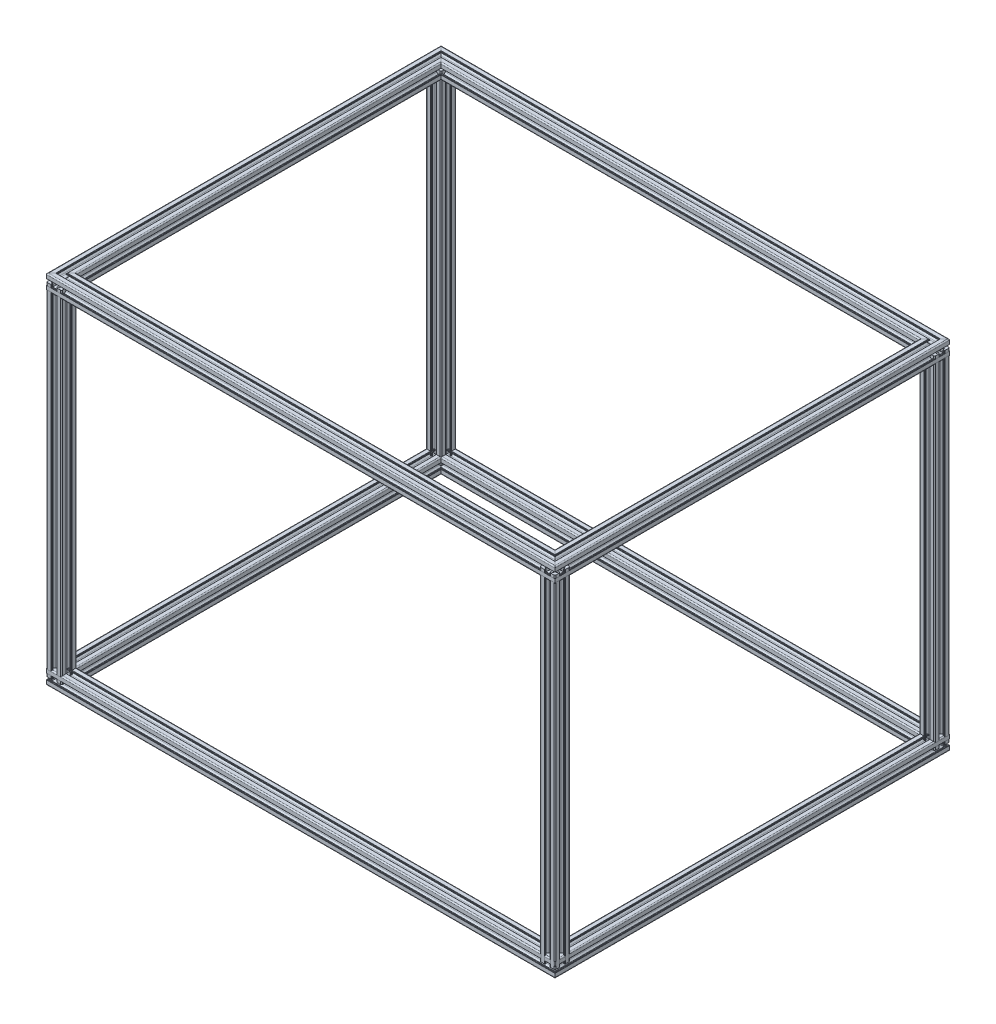
SolidWorks part; units mm, degrees
ref_plane "前视基准面" through (0, 0, 0) normal (0, 0, 1) x (1, 0, 0)
ref_plane "上视基准面" through (0, 0, 0) normal (0, 1, 0) x (1, 0, 0)
ref_plane "右视基准面" through (0, 0, 0) normal (1, 0, 0) x (0, 0, -1)
sketch3d "3D草图1"
  line L0 (0, 0, 0) -> (0, 0, 500)
  line L1 (0, 0, 500) -> (650, 0, 500)
  line L2 (0, 0, 0) -> (650, 0, 0)
  line L3 (650, 0, 0) -> (650, 0, 500)
  line L4 (0, 0, 0) -> (0, -450, 0)
  line L5 (0, -450, 0) -> (0, -450, 500)
  line L6 (0, -450, 500) -> (650, -450, 500)
  line L7 (650, -450, 500) -> (650, -450, 0)
  line L8 (0, -450, 0) -> (650, -450, 0)
  line L9 (0, 0, 500) -> (0, -450, 500)
  line L10 (650, 0, 500) -> (650, -450, 500)
  line L11 (650, 0, 0) -> (650, -450, 0)
  dimension "D1" = 650
  dimension "D2" = 650
  dimension "D3" = 500
  dimension "D4" = 650
  dimension "D5" = 650
  dimension "D6" = 500
  dimension "D7" = 450
other "铝型材库 2020(1)" corner treatment miter
ref_plane "基准面5" through (0, 0, 500) normal (1, 0, 0) x (0, 0, -1)
sketch "草图1" plane through (0, 0, 500) normal (1, 0, 0) x (0, 0, -1)
  line L0 (3.9, 0) -> (3.9, -2.0109)
  line L1 (4.4858, -3.4251) -> (6.5607, -5.5)
  line L2 (6.5607, -5.5) -> (7.9, -5.5)
  line L3 (8.2, -5.2) -> (8.2, -3.4)
  line L4 (8.5, -3.1) -> (9.2, -3.1)
  line L5 (9.5, -3.4) -> (9.5, -3.6)
  line L6 (9.5, -3.6) -> (9.7, -3.6)
  line L7 (10, -3.9) -> (10, -8.5)
  line L8 (8.5, -10) -> (3.9, -10)
  line L9 (3.1, -9.2) -> (3.1, -8.5)
  line L10 (3.4, -8.2) -> (5.2, -8.2)
  line L11 (5.5, -7.9) -> (5.5, -6.6849)
  line L12 (5.4121, -6.4728) -> (3.4251, -4.4858)
  line L13 (2.0109, -3.9) -> (0, -3.9)
  line L14 (0, -3.9) -> (-2.0109, -3.9)
  line L15 (-3.4251, -4.4858) -> (-5.4121, -6.4728)
  line L16 (-5.5, -6.6849) -> (-5.5, -7.9)
  line L17 (-5.2, -8.2) -> (-3.4, -8.2)
  line L18 (-3.1, -8.5) -> (-3.1, -9.2)
  line L19 (-3.9, -10) -> (-8.5, -10)
  line L20 (-10, -8.5) -> (-10, -3.9)
  line L21 (-9.7, -3.6) -> (-9.5, -3.6)
  line L22 (-9.5, -3.6) -> (-9.5, -3.4)
  line L23 (-9.2, -3.1) -> (-8.5, -3.1)
  line L24 (-8.2, -3.4) -> (-8.2, -5.2)
  line L25 (-7.9, -5.5) -> (-6.6849, -5.5)
  line L26 (-6.4728, -5.4121) -> (-4.4858, -3.4251)
  line L27 (-3.9, -2.0109) -> (-3.9, 0)
  line L28 (-3.9, 0) -> (-3.9, 2.0109)
  line L29 (-4.4858, 3.4251) -> (-6.4728, 5.4121)
  line L30 (-6.6849, 5.5) -> (-7.9, 5.5)
  line L31 (-8.2, 5.2) -> (-8.2, 3.4)
  line L32 (-8.5, 3.1) -> (-9.2, 3.1)
  line L33 (-9.5, 3.4) -> (-9.5, 3.6)
  line L34 (-9.5, 3.6) -> (-9.7, 3.6)
  line L35 (-10, 3.9) -> (-10, 8.5)
  line L36 (-8.5, 10) -> (-3.9, 10)
  line L37 (-3.6, 9.7) -> (-3.6, 9.5)
  line L38 (-3.6, 9.5) -> (-3.4, 9.5)
  line L39 (-3.1, 9.2) -> (-3.1, 8.5)
  line L40 (-3.4, 8.2) -> (-5.2, 8.2)
  line L41 (-5.5, 7.9) -> (-5.5, 6.6849)
  line L42 (-5.4121, 6.4728) -> (-3.4251, 4.4858)
  line L43 (-2.0109, 3.9) -> (0, 3.9)
  line L44 (0, 3.9) -> (2.0109, 3.9)
  line L45 (3.4251, 4.4858) -> (5.4121, 6.4728)
  line L46 (5.5, 6.6849) -> (5.5, 7.9)
  line L47 (5.2, 8.2) -> (3.4, 8.2)
  line L48 (3.1, 8.5) -> (3.1, 9.2)
  line L49 (3.4, 9.5) -> (3.6, 9.5)
  line L50 (3.6, 9.5) -> (3.6, 9.7)
  line L51 (3.9, 10) -> (8.5, 10)
  line L52 (10, 8.5) -> (10, 3.9)
  line L53 (9.7, 3.6) -> (9.5, 3.6)
  line L54 (9.5, 3.6) -> (9.5, 3.4)
  line L55 (9.2, 3.1) -> (8.5, 3.1)
  line L56 (8.2, 3.4) -> (8.2, 5.2)
  line L57 (7.9, 5.5) -> (6.6849, 5.5)
  line L58 (6.4728, 5.4121) -> (4.4858, 3.4251)
  line L59 (3.9, 2.0109) -> (3.9, 0)
  circle A0 centre (0, 0) radius 2.5
  arc A1 (3.9, -2.0109) -> (4.4858, -3.4251) centre (5.9, -2.0109) ccw
  arc A2 (7.9, -5.5) -> (8.2, -5.2) centre (7.9, -5.2) ccw
  arc A3 (8.5, -3.1) -> (8.2, -3.4) centre (8.5, -3.4) ccw
  arc A4 (9.5, -3.4) -> (9.2, -3.1) centre (9.2, -3.4) ccw
  arc A5 (10, -3.9) -> (9.7, -3.6) centre (9.7, -3.9) ccw
  arc A6 (8.5, -10) -> (10, -8.5) centre (8.5, -8.5) ccw
  arc A7 (3.6, -9.7) -> (3.9, -10) centre (3.9, -9.7) ccw
  arc A8 (3.6, -9.7) -> (3.4, -9.5) centre (3.4, -9.7) ccw
  arc A9 (3.1, -9.2) -> (3.4, -9.5) centre (3.4, -9.2) ccw
  arc A10 (3.4, -8.2) -> (3.1, -8.5) centre (3.4, -8.5) ccw
  arc A11 (5.2, -8.2) -> (5.5, -7.9) centre (5.2, -7.9) ccw
  arc A12 (5.5, -6.6849) -> (5.4121, -6.4728) centre (5.2, -6.6849) ccw
  arc A13 (3.4251, -4.4858) -> (2.0109, -3.9) centre (2.0109, -5.9) ccw
  arc A14 (-2.0109, -3.9) -> (-3.4251, -4.4858) centre (-2.0109, -5.9) ccw
  arc A15 (-5.4121, -6.4728) -> (-5.5, -6.6849) centre (-5.2, -6.6849) ccw
  arc A16 (-5.5, -7.9) -> (-5.2, -8.2) centre (-5.2, -7.9) ccw
  arc A17 (-3.1, -8.5) -> (-3.4, -8.2) centre (-3.4, -8.5) ccw
  arc A18 (-3.4, -9.5) -> (-3.1, -9.2) centre (-3.4, -9.2) ccw
  arc A19 (-3.4, -9.5) -> (-3.6, -9.7) centre (-3.4, -9.7) ccw
  arc A20 (-3.9, -10) -> (-3.6, -9.7) centre (-3.9, -9.7) ccw
  arc A21 (-10, -8.5) -> (-8.5, -10) centre (-8.5, -8.5) ccw
  arc A22 (-9.7, -3.6) -> (-10, -3.9) centre (-9.7, -3.9) ccw
  arc A23 (-9.2, -3.1) -> (-9.5, -3.4) centre (-9.2, -3.4) ccw
  arc A24 (-8.2, -3.4) -> (-8.5, -3.1) centre (-8.5, -3.4) ccw
  arc A25 (-8.2, -5.2) -> (-7.9, -5.5) centre (-7.9, -5.2) ccw
  arc A26 (-6.6849, -5.5) -> (-6.4728, -5.4121) centre (-6.6849, -5.2) ccw
  arc A27 (-4.4858, -3.4251) -> (-3.9, -2.0109) centre (-5.9, -2.0109) ccw
  arc A28 (-3.9, 2.0109) -> (-4.4858, 3.4251) centre (-5.9, 2.0109) ccw
  arc A29 (-6.4728, 5.4121) -> (-6.6849, 5.5) centre (-6.6849, 5.2) ccw
  arc A30 (-7.9, 5.5) -> (-8.2, 5.2) centre (-7.9, 5.2) ccw
  arc A31 (-8.5, 3.1) -> (-8.2, 3.4) centre (-8.5, 3.4) ccw
  arc A32 (-9.5, 3.4) -> (-9.2, 3.1) centre (-9.2, 3.4) ccw
  arc A33 (-10, 3.9) -> (-9.7, 3.6) centre (-9.7, 3.9) ccw
  arc A34 (-8.5, 10) -> (-10, 8.5) centre (-8.5, 8.5) ccw
  arc A35 (-3.6, 9.7) -> (-3.9, 10) centre (-3.9, 9.7) ccw
  arc A36 (-3.1, 9.2) -> (-3.4, 9.5) centre (-3.4, 9.2) ccw
  arc A37 (-3.4, 8.2) -> (-3.1, 8.5) centre (-3.4, 8.5) ccw
  arc A38 (-5.2, 8.2) -> (-5.5, 7.9) centre (-5.2, 7.9) ccw
  arc A39 (-5.5, 6.6849) -> (-5.4121, 6.4728) centre (-5.2, 6.6849) ccw
  arc A40 (-3.4251, 4.4858) -> (-2.0109, 3.9) centre (-2.0109, 5.9) ccw
  arc A41 (2.0109, 3.9) -> (3.4251, 4.4858) centre (2.0109, 5.9) ccw
  arc A42 (5.4121, 6.4728) -> (5.5, 6.6849) centre (5.2, 6.6849) ccw
  arc A43 (5.5, 7.9) -> (5.2, 8.2) centre (5.2, 7.9) ccw
  arc A44 (3.1, 8.5) -> (3.4, 8.2) centre (3.4, 8.5) ccw
  arc A45 (3.4, 9.5) -> (3.1, 9.2) centre (3.4, 9.2) ccw
  arc A46 (3.9, 10) -> (3.6, 9.7) centre (3.9, 9.7) ccw
  arc A47 (10, 8.5) -> (8.5, 10) centre (8.5, 8.5) ccw
  arc A48 (9.7, 3.6) -> (10, 3.9) centre (9.7, 3.9) ccw
  arc A49 (9.2, 3.1) -> (9.5, 3.4) centre (9.2, 3.4) ccw
  arc A50 (8.2, 3.4) -> (8.5, 3.1) centre (8.5, 3.4) ccw
  arc A51 (8.2, 5.2) -> (7.9, 5.5) centre (7.9, 5.2) ccw
  arc A52 (6.6849, 5.5) -> (6.4728, 5.4121) centre (6.6849, 5.2) ccw
  arc A53 (4.4858, 3.4251) -> (3.9, 2.0109) centre (5.9, 2.0109) ccw
  point P0 (0, 0)
other "铝型材库 2020(2)" corner treatment miter
ref_plane "基准面6" through (650, -450, 500) normal (0, 0, -1) x (1, 0, 0)
sketch "草图113" plane through (650, -450, 500) normal (0, 0, -1) x (1, 0, 0)
  line L0 (3.9, 0) -> (3.9, -2.0109)
  line L1 (4.4858, -3.4251) -> (6.5607, -5.5)
  line L2 (6.5607, -5.5) -> (7.9, -5.5)
  line L3 (8.2, -5.2) -> (8.2, -3.4)
  line L4 (8.5, -3.1) -> (9.2, -3.1)
  line L5 (9.5, -3.4) -> (9.5, -3.6)
  line L6 (9.5, -3.6) -> (9.7, -3.6)
  line L7 (10, -3.9) -> (10, -8.5)
  line L8 (8.5, -10) -> (3.9, -10)
  line L9 (3.1, -9.2) -> (3.1, -8.5)
  line L10 (3.4, -8.2) -> (5.2, -8.2)
  line L11 (5.5, -7.9) -> (5.5, -6.6849)
  line L12 (5.4121, -6.4728) -> (3.4251, -4.4858)
  line L13 (2.0109, -3.9) -> (0, -3.9)
  line L14 (0, -3.9) -> (-2.0109, -3.9)
  line L15 (-3.4251, -4.4858) -> (-5.4121, -6.4728)
  line L16 (-5.5, -6.6849) -> (-5.5, -7.9)
  line L17 (-5.2, -8.2) -> (-3.4, -8.2)
  line L18 (-3.1, -8.5) -> (-3.1, -9.2)
  line L19 (-3.9, -10) -> (-8.5, -10)
  line L20 (-10, -8.5) -> (-10, -3.9)
  line L21 (-9.7, -3.6) -> (-9.5, -3.6)
  line L22 (-9.5, -3.6) -> (-9.5, -3.4)
  line L23 (-9.2, -3.1) -> (-8.5, -3.1)
  line L24 (-8.2, -3.4) -> (-8.2, -5.2)
  line L25 (-7.9, -5.5) -> (-6.6849, -5.5)
  line L26 (-6.4728, -5.4121) -> (-4.4858, -3.4251)
  line L27 (-3.9, -2.0109) -> (-3.9, 0)
  line L28 (-3.9, 0) -> (-3.9, 2.0109)
  line L29 (-4.4858, 3.4251) -> (-6.4728, 5.4121)
  line L30 (-6.6849, 5.5) -> (-7.9, 5.5)
  line L31 (-8.2, 5.2) -> (-8.2, 3.4)
  line L32 (-8.5, 3.1) -> (-9.2, 3.1)
  line L33 (-9.5, 3.4) -> (-9.5, 3.6)
  line L34 (-9.5, 3.6) -> (-9.7, 3.6)
  line L35 (-10, 3.9) -> (-10, 8.5)
  line L36 (-8.5, 10) -> (-3.9, 10)
  line L37 (-3.6, 9.7) -> (-3.6, 9.5)
  line L38 (-3.6, 9.5) -> (-3.4, 9.5)
  line L39 (-3.1, 9.2) -> (-3.1, 8.5)
  line L40 (-3.4, 8.2) -> (-5.2, 8.2)
  line L41 (-5.5, 7.9) -> (-5.5, 6.6849)
  line L42 (-5.4121, 6.4728) -> (-3.4251, 4.4858)
  line L43 (-2.0109, 3.9) -> (0, 3.9)
  line L44 (0, 3.9) -> (2.0109, 3.9)
  line L45 (3.4251, 4.4858) -> (5.4121, 6.4728)
  line L46 (5.5, 6.6849) -> (5.5, 7.9)
  line L47 (5.2, 8.2) -> (3.4, 8.2)
  line L48 (3.1, 8.5) -> (3.1, 9.2)
  line L49 (3.4, 9.5) -> (3.6, 9.5)
  line L50 (3.6, 9.5) -> (3.6, 9.7)
  line L51 (3.9, 10) -> (8.5, 10)
  line L52 (10, 8.5) -> (10, 3.9)
  line L53 (9.7, 3.6) -> (9.5, 3.6)
  line L54 (9.5, 3.6) -> (9.5, 3.4)
  line L55 (9.2, 3.1) -> (8.5, 3.1)
  line L56 (8.2, 3.4) -> (8.2, 5.2)
  line L57 (7.9, 5.5) -> (6.6849, 5.5)
  line L58 (6.4728, 5.4121) -> (4.4858, 3.4251)
  line L59 (3.9, 2.0109) -> (3.9, 0)
  circle A0 centre (0, 0) radius 2.5
  arc A1 (3.9, -2.0109) -> (4.4858, -3.4251) centre (5.9, -2.0109) ccw
  arc A2 (7.9, -5.5) -> (8.2, -5.2) centre (7.9, -5.2) ccw
  arc A3 (8.5, -3.1) -> (8.2, -3.4) centre (8.5, -3.4) ccw
  arc A4 (9.5, -3.4) -> (9.2, -3.1) centre (9.2, -3.4) ccw
  arc A5 (10, -3.9) -> (9.7, -3.6) centre (9.7, -3.9) ccw
  arc A6 (8.5, -10) -> (10, -8.5) centre (8.5, -8.5) ccw
  arc A7 (3.6, -9.7) -> (3.9, -10) centre (3.9, -9.7) ccw
  arc A8 (3.6, -9.7) -> (3.4, -9.5) centre (3.4, -9.7) ccw
  arc A9 (3.1, -9.2) -> (3.4, -9.5) centre (3.4, -9.2) ccw
  arc A10 (3.4, -8.2) -> (3.1, -8.5) centre (3.4, -8.5) ccw
  arc A11 (5.2, -8.2) -> (5.5, -7.9) centre (5.2, -7.9) ccw
  arc A12 (5.5, -6.6849) -> (5.4121, -6.4728) centre (5.2, -6.6849) ccw
  arc A13 (3.4251, -4.4858) -> (2.0109, -3.9) centre (2.0109, -5.9) ccw
  arc A14 (-2.0109, -3.9) -> (-3.4251, -4.4858) centre (-2.0109, -5.9) ccw
  arc A15 (-5.4121, -6.4728) -> (-5.5, -6.6849) centre (-5.2, -6.6849) ccw
  arc A16 (-5.5, -7.9) -> (-5.2, -8.2) centre (-5.2, -7.9) ccw
  arc A17 (-3.1, -8.5) -> (-3.4, -8.2) centre (-3.4, -8.5) ccw
  arc A18 (-3.4, -9.5) -> (-3.1, -9.2) centre (-3.4, -9.2) ccw
  arc A19 (-3.4, -9.5) -> (-3.6, -9.7) centre (-3.4, -9.7) ccw
  arc A20 (-3.9, -10) -> (-3.6, -9.7) centre (-3.9, -9.7) ccw
  arc A21 (-10, -8.5) -> (-8.5, -10) centre (-8.5, -8.5) ccw
  arc A22 (-9.7, -3.6) -> (-10, -3.9) centre (-9.7, -3.9) ccw
  arc A23 (-9.2, -3.1) -> (-9.5, -3.4) centre (-9.2, -3.4) ccw
  arc A24 (-8.2, -3.4) -> (-8.5, -3.1) centre (-8.5, -3.4) ccw
  arc A25 (-8.2, -5.2) -> (-7.9, -5.5) centre (-7.9, -5.2) ccw
  arc A26 (-6.6849, -5.5) -> (-6.4728, -5.4121) centre (-6.6849, -5.2) ccw
  arc A27 (-4.4858, -3.4251) -> (-3.9, -2.0109) centre (-5.9, -2.0109) ccw
  arc A28 (-3.9, 2.0109) -> (-4.4858, 3.4251) centre (-5.9, 2.0109) ccw
  arc A29 (-6.4728, 5.4121) -> (-6.6849, 5.5) centre (-6.6849, 5.2) ccw
  arc A30 (-7.9, 5.5) -> (-8.2, 5.2) centre (-7.9, 5.2) ccw
  arc A31 (-8.5, 3.1) -> (-8.2, 3.4) centre (-8.5, 3.4) ccw
  arc A32 (-9.5, 3.4) -> (-9.2, 3.1) centre (-9.2, 3.4) ccw
  arc A33 (-10, 3.9) -> (-9.7, 3.6) centre (-9.7, 3.9) ccw
  arc A34 (-8.5, 10) -> (-10, 8.5) centre (-8.5, 8.5) ccw
  arc A35 (-3.6, 9.7) -> (-3.9, 10) centre (-3.9, 9.7) ccw
  arc A36 (-3.1, 9.2) -> (-3.4, 9.5) centre (-3.4, 9.2) ccw
  arc A37 (-3.4, 8.2) -> (-3.1, 8.5) centre (-3.4, 8.5) ccw
  arc A38 (-5.2, 8.2) -> (-5.5, 7.9) centre (-5.2, 7.9) ccw
  arc A39 (-5.5, 6.6849) -> (-5.4121, 6.4728) centre (-5.2, 6.6849) ccw
  arc A40 (-3.4251, 4.4858) -> (-2.0109, 3.9) centre (-2.0109, 5.9) ccw
  arc A41 (2.0109, 3.9) -> (3.4251, 4.4858) centre (2.0109, 5.9) ccw
  arc A42 (5.4121, 6.4728) -> (5.5, 6.6849) centre (5.2, 6.6849) ccw
  arc A43 (5.5, 7.9) -> (5.2, 8.2) centre (5.2, 7.9) ccw
  arc A44 (3.1, 8.5) -> (3.4, 8.2) centre (3.4, 8.5) ccw
  arc A45 (3.4, 9.5) -> (3.1, 9.2) centre (3.4, 9.2) ccw
  arc A46 (3.9, 10) -> (3.6, 9.7) centre (3.9, 9.7) ccw
  arc A47 (10, 8.5) -> (8.5, 10) centre (8.5, 8.5) ccw
  arc A48 (9.7, 3.6) -> (10, 3.9) centre (9.7, 3.9) ccw
  arc A49 (9.2, 3.1) -> (9.5, 3.4) centre (9.2, 3.4) ccw
  arc A50 (8.2, 3.4) -> (8.5, 3.1) centre (8.5, 3.4) ccw
  arc A51 (8.2, 5.2) -> (7.9, 5.5) centre (7.9, 5.2) ccw
  arc A52 (6.6849, 5.5) -> (6.4728, 5.4121) centre (6.6849, 5.2) ccw
  arc A53 (4.4858, 3.4251) -> (3.9, 2.0109) centre (5.9, 2.0109) ccw
  point P0 (0, 0)
other "铝型材库 2020(3)" corner treatment miter
ref_plane "基准面7" through (650, 0, 500) normal (0, -1, 0) x (1, 0, 0)
sketch "草图114" plane through (650, 0, 500) normal (0, -1, 0) x (1, 0, 0)
  line L0 (3.9, 0) -> (3.9, -2.0109)
  line L1 (4.4858, -3.4251) -> (6.5607, -5.5)
  line L2 (6.5607, -5.5) -> (7.9, -5.5)
  line L3 (8.2, -5.2) -> (8.2, -3.4)
  line L4 (8.5, -3.1) -> (9.2, -3.1)
  line L5 (9.5, -3.4) -> (9.5, -3.6)
  line L6 (9.5, -3.6) -> (9.7, -3.6)
  line L7 (10, -3.9) -> (10, -8.5)
  line L8 (8.5, -10) -> (3.9, -10)
  line L9 (3.1, -9.2) -> (3.1, -8.5)
  line L10 (3.4, -8.2) -> (5.2, -8.2)
  line L11 (5.5, -7.9) -> (5.5, -6.6849)
  line L12 (5.4121, -6.4728) -> (3.4251, -4.4858)
  line L13 (2.0109, -3.9) -> (0, -3.9)
  line L14 (0, -3.9) -> (-2.0109, -3.9)
  line L15 (-3.4251, -4.4858) -> (-5.4121, -6.4728)
  line L16 (-5.5, -6.6849) -> (-5.5, -7.9)
  line L17 (-5.2, -8.2) -> (-3.4, -8.2)
  line L18 (-3.1, -8.5) -> (-3.1, -9.2)
  line L19 (-3.9, -10) -> (-8.5, -10)
  line L20 (-10, -8.5) -> (-10, -3.9)
  line L21 (-9.7, -3.6) -> (-9.5, -3.6)
  line L22 (-9.5, -3.6) -> (-9.5, -3.4)
  line L23 (-9.2, -3.1) -> (-8.5, -3.1)
  line L24 (-8.2, -3.4) -> (-8.2, -5.2)
  line L25 (-7.9, -5.5) -> (-6.6849, -5.5)
  line L26 (-6.4728, -5.4121) -> (-4.4858, -3.4251)
  line L27 (-3.9, -2.0109) -> (-3.9, 0)
  line L28 (-3.9, 0) -> (-3.9, 2.0109)
  line L29 (-4.4858, 3.4251) -> (-6.4728, 5.4121)
  line L30 (-6.6849, 5.5) -> (-7.9, 5.5)
  line L31 (-8.2, 5.2) -> (-8.2, 3.4)
  line L32 (-8.5, 3.1) -> (-9.2, 3.1)
  line L33 (-9.5, 3.4) -> (-9.5, 3.6)
  line L34 (-9.5, 3.6) -> (-9.7, 3.6)
  line L35 (-10, 3.9) -> (-10, 8.5)
  line L36 (-8.5, 10) -> (-3.9, 10)
  line L37 (-3.6, 9.7) -> (-3.6, 9.5)
  line L38 (-3.6, 9.5) -> (-3.4, 9.5)
  line L39 (-3.1, 9.2) -> (-3.1, 8.5)
  line L40 (-3.4, 8.2) -> (-5.2, 8.2)
  line L41 (-5.5, 7.9) -> (-5.5, 6.6849)
  line L42 (-5.4121, 6.4728) -> (-3.4251, 4.4858)
  line L43 (-2.0109, 3.9) -> (0, 3.9)
  line L44 (0, 3.9) -> (2.0109, 3.9)
  line L45 (3.4251, 4.4858) -> (5.4121, 6.4728)
  line L46 (5.5, 6.6849) -> (5.5, 7.9)
  line L47 (5.2, 8.2) -> (3.4, 8.2)
  line L48 (3.1, 8.5) -> (3.1, 9.2)
  line L49 (3.4, 9.5) -> (3.6, 9.5)
  line L50 (3.6, 9.5) -> (3.6, 9.7)
  line L51 (3.9, 10) -> (8.5, 10)
  line L52 (10, 8.5) -> (10, 3.9)
  line L53 (9.7, 3.6) -> (9.5, 3.6)
  line L54 (9.5, 3.6) -> (9.5, 3.4)
  line L55 (9.2, 3.1) -> (8.5, 3.1)
  line L56 (8.2, 3.4) -> (8.2, 5.2)
  line L57 (7.9, 5.5) -> (6.6849, 5.5)
  line L58 (6.4728, 5.4121) -> (4.4858, 3.4251)
  line L59 (3.9, 2.0109) -> (3.9, 0)
  circle A0 centre (0, 0) radius 2.5
  arc A1 (3.9, -2.0109) -> (4.4858, -3.4251) centre (5.9, -2.0109) ccw
  arc A2 (7.9, -5.5) -> (8.2, -5.2) centre (7.9, -5.2) ccw
  arc A3 (8.5, -3.1) -> (8.2, -3.4) centre (8.5, -3.4) ccw
  arc A4 (9.5, -3.4) -> (9.2, -3.1) centre (9.2, -3.4) ccw
  arc A5 (10, -3.9) -> (9.7, -3.6) centre (9.7, -3.9) ccw
  arc A6 (8.5, -10) -> (10, -8.5) centre (8.5, -8.5) ccw
  arc A7 (3.6, -9.7) -> (3.9, -10) centre (3.9, -9.7) ccw
  arc A8 (3.6, -9.7) -> (3.4, -9.5) centre (3.4, -9.7) ccw
  arc A9 (3.1, -9.2) -> (3.4, -9.5) centre (3.4, -9.2) ccw
  arc A10 (3.4, -8.2) -> (3.1, -8.5) centre (3.4, -8.5) ccw
  arc A11 (5.2, -8.2) -> (5.5, -7.9) centre (5.2, -7.9) ccw
  arc A12 (5.5, -6.6849) -> (5.4121, -6.4728) centre (5.2, -6.6849) ccw
  arc A13 (3.4251, -4.4858) -> (2.0109, -3.9) centre (2.0109, -5.9) ccw
  arc A14 (-2.0109, -3.9) -> (-3.4251, -4.4858) centre (-2.0109, -5.9) ccw
  arc A15 (-5.4121, -6.4728) -> (-5.5, -6.6849) centre (-5.2, -6.6849) ccw
  arc A16 (-5.5, -7.9) -> (-5.2, -8.2) centre (-5.2, -7.9) ccw
  arc A17 (-3.1, -8.5) -> (-3.4, -8.2) centre (-3.4, -8.5) ccw
  arc A18 (-3.4, -9.5) -> (-3.1, -9.2) centre (-3.4, -9.2) ccw
  arc A19 (-3.4, -9.5) -> (-3.6, -9.7) centre (-3.4, -9.7) ccw
  arc A20 (-3.9, -10) -> (-3.6, -9.7) centre (-3.9, -9.7) ccw
  arc A21 (-10, -8.5) -> (-8.5, -10) centre (-8.5, -8.5) ccw
  arc A22 (-9.7, -3.6) -> (-10, -3.9) centre (-9.7, -3.9) ccw
  arc A23 (-9.2, -3.1) -> (-9.5, -3.4) centre (-9.2, -3.4) ccw
  arc A24 (-8.2, -3.4) -> (-8.5, -3.1) centre (-8.5, -3.4) ccw
  arc A25 (-8.2, -5.2) -> (-7.9, -5.5) centre (-7.9, -5.2) ccw
  arc A26 (-6.6849, -5.5) -> (-6.4728, -5.4121) centre (-6.6849, -5.2) ccw
  arc A27 (-4.4858, -3.4251) -> (-3.9, -2.0109) centre (-5.9, -2.0109) ccw
  arc A28 (-3.9, 2.0109) -> (-4.4858, 3.4251) centre (-5.9, 2.0109) ccw
  arc A29 (-6.4728, 5.4121) -> (-6.6849, 5.5) centre (-6.6849, 5.2) ccw
  arc A30 (-7.9, 5.5) -> (-8.2, 5.2) centre (-7.9, 5.2) ccw
  arc A31 (-8.5, 3.1) -> (-8.2, 3.4) centre (-8.5, 3.4) ccw
  arc A32 (-9.5, 3.4) -> (-9.2, 3.1) centre (-9.2, 3.4) ccw
  arc A33 (-10, 3.9) -> (-9.7, 3.6) centre (-9.7, 3.9) ccw
  arc A34 (-8.5, 10) -> (-10, 8.5) centre (-8.5, 8.5) ccw
  arc A35 (-3.6, 9.7) -> (-3.9, 10) centre (-3.9, 9.7) ccw
  arc A36 (-3.1, 9.2) -> (-3.4, 9.5) centre (-3.4, 9.2) ccw
  arc A37 (-3.4, 8.2) -> (-3.1, 8.5) centre (-3.4, 8.5) ccw
  arc A38 (-5.2, 8.2) -> (-5.5, 7.9) centre (-5.2, 7.9) ccw
  arc A39 (-5.5, 6.6849) -> (-5.4121, 6.4728) centre (-5.2, 6.6849) ccw
  arc A40 (-3.4251, 4.4858) -> (-2.0109, 3.9) centre (-2.0109, 5.9) ccw
  arc A41 (2.0109, 3.9) -> (3.4251, 4.4858) centre (2.0109, 5.9) ccw
  arc A42 (5.4121, 6.4728) -> (5.5, 6.6849) centre (5.2, 6.6849) ccw
  arc A43 (5.5, 7.9) -> (5.2, 8.2) centre (5.2, 7.9) ccw
  arc A44 (3.1, 8.5) -> (3.4, 8.2) centre (3.4, 8.5) ccw
  arc A45 (3.4, 9.5) -> (3.1, 9.2) centre (3.4, 9.2) ccw
  arc A46 (3.9, 10) -> (3.6, 9.7) centre (3.9, 9.7) ccw
  arc A47 (10, 8.5) -> (8.5, 10) centre (8.5, 8.5) ccw
  arc A48 (9.7, 3.6) -> (10, 3.9) centre (9.7, 3.9) ccw
  arc A49 (9.2, 3.1) -> (9.5, 3.4) centre (9.2, 3.4) ccw
  arc A50 (8.2, 3.4) -> (8.5, 3.1) centre (8.5, 3.4) ccw
  arc A51 (8.2, 5.2) -> (7.9, 5.5) centre (7.9, 5.2) ccw
  arc A52 (6.6849, 5.5) -> (6.4728, 5.4121) centre (6.6849, 5.2) ccw
  arc A53 (4.4858, 3.4251) -> (3.9, 2.0109) centre (5.9, 2.0109) ccw
  point P0 (0, 0)
